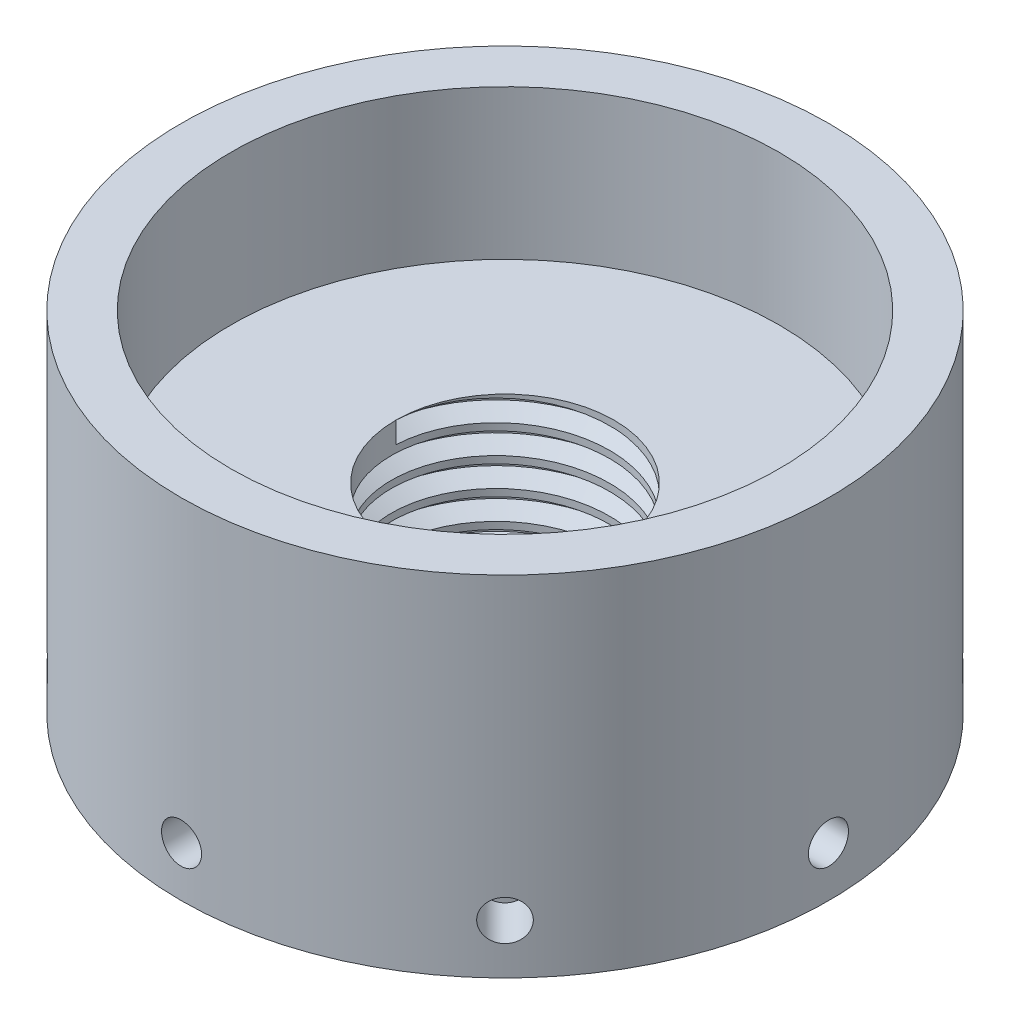
SolidWorks part; units mm, degrees
material "1060 Alloy"
ref_plane "Front Plane" through (0, 0, 0) normal (0, 0, 1) x (1, 0, 0)
ref_plane "Top Plane" through (0, 0, 0) normal (0, 1, 0) x (1, 0, 0)
ref_plane "Right Plane" through (0, 0, 0) normal (1, 0, 0) x (0, 0, -1)
sketch "Sketch1" plane through (0, 0, 0) normal (0, 0, 1) x (1, 0, 0)
  line L0 (0, 0) -> (0, 25.4) construction
  line L1 (-41.275, -44.45) -> (-41.275, 0)
  line L2 (-20.32, -52.832) -> (-20.32, -31.75)
  line L3 (-8.9065, -52.832) -> (-8.9065, -39.37)
  line L4 (-13.9116, -19.05) -> (-34.925, -19.05)
  line L5 (-34.925, -19.05) -> (-34.925, 0)
  line L6 (-34.925, 0) -> (-41.275, 0)
  line L8 (-8.9065, -52.832) -> (-20.32, -52.832)
  line L9 (55, 0) -> (-55, 0) construction
  line L10 (-41.275, -44.45) -> (-34.925, -44.45)
  line L11 (-20.32, -31.75) -> (-34.925, -31.75)
  line L12 (-34.925, -44.45) -> (-34.925, -31.75)
  line L13 (-13.9116, -39.37) -> (-13.9116, -19.05)
  line L14 (-8.9065, -39.37) -> (-13.9116, -39.37)
  dimension "D6" = 8.9065
  dimension "D7" = 13.462
  dimension "D9" = 12.7
  dimension "D8" = 20.32
  dimension "D2" = 34.925
  dimension "D3" = 44.45
  dimension "D4" = 6.35
  dimension "D5" = 20.32
  dimension "D10" = 13.9116
  dimension "D11" = 12.7
revolve "Revolve1" add sketch "Sketch1" angle 360 about L0
ref_plane "Plane1" through (0, 0, 0) normal (-1, 0, 0) x (0, 0, -1)
ref_plane "Plane2" through (0, 0, 0) normal (-1, 0, 0) x (0, 0, -1)
ref_plane "Plane3" through (0, 0, 0) normal (-1, 0, 0) x (0, 0, -1)
ref_plane "Plane4" through (0, 0, 0) normal (-1, 0, 0) x (0, 0, -1)
ref_plane "Plane5" through (0, 0, 0) normal (-1, 0, 0) x (0, 0, -1)
ref_plane "Plane6" through (0, 0, 0) normal (-1, 0, 0) x (0, 0, -1)
ref_plane "Plane7" through (0, 0, 0) normal (-1, 0, 0) x (0, 0, -1)
ref_plane "Plane8" through (0, 0, 0) normal (-1, 0, 0) x (0, 0, -1)
ref_plane "Plane9" through (0, 0, 0) normal (-1, 0, 0) x (0, 0, -1)
ref_plane "Plane10" through (0, 0, 0) normal (-1, 0, 0) x (0, 0, -1)
ref_plane "Plane11" through (0, 0, 0) normal (-1, 0, 0) x (0, 0, -1)
ref_plane "Plane12" through (0, -38.1, 0) normal (0, -1, 0) x (-1, 0, 0)
ref_axis "Axis1" through (-88.99, -38.1, 0) along (1, 0, 0)
ref_axis "Axis2" through (0, -65.0537, 0) along (0, 1, 0)
hole_wizard "1/4-20 Tapped Hole1" positions "3DSketch1" profile "Sketch8" tap size "1/4-20" standard "ANSI Inch" end condition up to next
sketch3d "3DSketch1"
  line L0 (-88.99, -38.1, 0) -> (88.99, -38.1, 0) construction
  point P0 (41.275, -38.1, 0)
  point P3 (0, 0, 0)
sketch "Sketch8" plane through (41.275, -38.1, 0) normal (0, 1, 0) x (0, 0, -1)
  line L0 (0, 0) -> (0, 6.35)
  line L1 (0, 6.35) -> (2.5527, 6.35)
  line L2 (2.5527, 6.35) -> (2.5527, 0)
  line L5 (2.5527, 0) -> (0, 0)
  line L11 (0, -6.35) -> (0, 107.95) construction
  dimension "Thru Tap Drill Dia." = 5.1054
  dimension "Thru Tap Drill Depth" = 6.35
cosmetic thread "Hole Thread1" parameters "D2"=6.35
pattern_circular "CirPattern1" count 8 over 360 about axis through (0, -65.0537, 0) along (0, 1, 0) of "1/4-20 Tapped Hole1" reverse direction yes
thread "Thread1" pitch 3.6286 method cut profile "Thread Profile1" start angle 0, offset 0, length 0, pitch 3.6286, diameter 27.8232
ref_plane "Plane13" through (-13.9116, -19.05, 0) normal (0, 0, 1) x (-1, 0, 0)
sketch "Thread Profile1" plane through (-13.9116, -19.05, 0) normal (0, 0, 1) x (-1, 0, 0)
  line L0 (0, 0) -> (0, 3.6286) construction
  line L1 (0, 0) -> (1.964, 1.1339)
  line L2 (1.964, 1.1339) -> (1.964, 1.5875)
  line L3 (1.964, 1.5875) -> (0, 2.7214)
  line L4 (1.964, 1.3607) -> (0, 1.3607) construction
  line L11 (0, 0) -> (0, 2.7214)
  point P2 (0, 0)
  dimension "Pitch" = 3.6286
  dimension "Profile_Angle" = 60
  dimension "Profile_Land" = 0.4536
  dimension "Profile_Height" = 1.964
